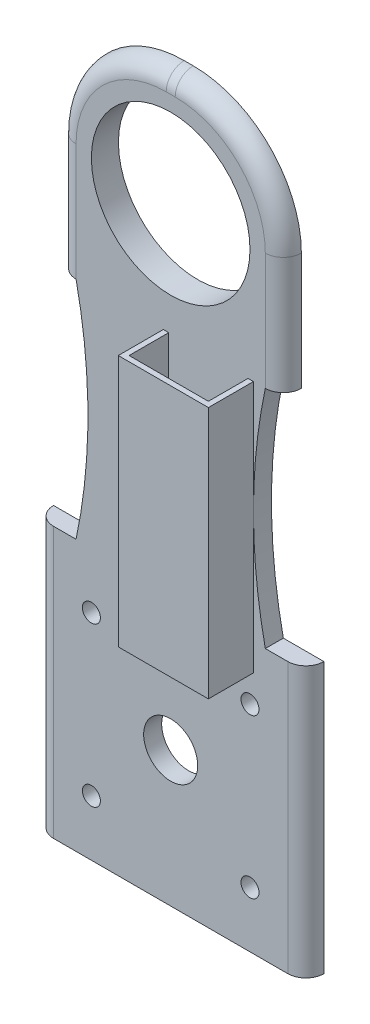
SolidWorks part; units mm, degrees
ref_plane "Front Plane" through (0, 0, 0) normal (0, 0, 1) x (1, 0, 0)
ref_plane "Top Plane" through (0, 0, 0) normal (0, 1, 0) x (1, 0, 0)
ref_plane "Right Plane" through (0, 0, 0) normal (1, 0, 0) x (0, 0, -1)
sketch "Sketch1" plane through (0, 0, 0) normal (0, 0, 1) x (1, 0, 0)
  line L0 (-13.335, -47.625) -> (-19.05, -47.625)
  line L1 (15.875, -15.875) -> (13.335, -15.875)
  line L2 (15.875, -15.875) -> (15.875, 0.635)
  line L3 (0.635, 15.875) -> (-0.635, 15.875)
  line L4 (-15.875, -15.875) -> (-15.875, 0.635)
  line L5 (15.875, -15.875) -> (-15.875, 15.875) construction
  line L6 (15.875, 15.875) -> (-15.875, -15.875) construction
  line L7 (19.05, -85.725) -> (-19.05, -85.725)
  line L8 (19.05, -85.725) -> (19.05, -47.625)
  line L9 (19.05, -47.625) -> (13.335, -47.625)
  line L10 (-19.05, -85.725) -> (-19.05, -47.625)
  line L11 (19.05, -85.725) -> (-19.05, -47.625) construction
  line L12 (19.05, -47.625) -> (-19.05, -85.725) construction
  line L13 (-13.335, -15.875) -> (-15.875, -15.875)
  line L15 (11.176, -77.851) -> (-11.176, -77.851) construction
  line L16 (11.176, -77.851) -> (11.176, -55.499) construction
  line L17 (11.176, -55.499) -> (-11.176, -55.499) construction
  line L18 (-11.176, -77.851) -> (-11.176, -55.499) construction
  line L19 (11.176, -77.851) -> (-11.176, -55.499) construction
  line L20 (11.176, -55.499) -> (-11.176, -77.851) construction
  arc A0 (0.635, 15.875) -> (15.875, 0.635) centre (0.635, 0.635) cw
  arc A1 (-15.875, 0.635) -> (-0.635, 15.875) centre (-0.635, 0.635) cw
  circle A2 centre (0, 0) radius 11.176
  arc A3 (13.335, -15.875) -> (13.335, -47.625) centre (87.863, -31.75) ccw
  arc A4 (-13.335, -15.875) -> (-13.335, -47.625) centre (-87.863, -31.75) cw
  circle A5 centre (11.176, -55.499) radius 1.27
  circle A6 centre (11.176, -77.851) radius 1.27
  circle A7 centre (-11.176, -77.851) radius 1.27
  circle A8 centre (-11.176, -55.499) radius 1.27
  circle A9 centre (0, -66.675) radius 3.81
  point P0 (0, 0)
  point P20 (0, -66.675)
  point P23 (0, -66.675)
  dimension "D3" = 15.24
  dimension "D4" = 22.352
  dimension "D6" = 76.2
  dimension "D11" = 2.54
  dimension "D12" = 7.62
  dimension "D1" = 31.75
  dimension "D2" = 31.75
  dimension "D5" = 31.75
  dimension "D7" = 2.54
  dimension "D8" = 2.54
  dimension "D9" = 38.1
  dimension "D10" = 22.352
extrude "Boss-Extrude1" add sketch "Sketch1" along normal blind 2.54
fillet "Fillet2" radius 2.54 2 edges at (19.05, -66.675, 2.54) (-19.05, -66.675, 2.54)
fillet "Fillet3" radius 2.54 5 edges at (15.875, -7.62, 2.54) (11.4113, 11.4113, 2.54) (0, 15.875, 2.54) (-11.4113, 11.4113, 2.54) (-15.875, -7.62, 2.54)
sketch "Sketch2" plane through (0, 0, 0) normal (0, 0, -1) x (-1, 0, 0)
  circle A0 centre (0, 0) radius 11.176
  circle A1 centre (0, 0) radius 13.716
  circle A2 centre (0, 0) radius 11.176 construction
  dimension "D1" = 2.54
extrude "Boss-Extrude2" add sketch "Sketch2" along normal blind 1.27
sketch "Sketch3" plane through (0, 0, 2.54) normal (0, 0, 1) x (1, 0, 0)
  line L0 (13.335, -15.875) -> (15.875, -15.875) construction
  line L1 (3.535, -22.225) -> (10.901, -22.225)
  line L2 (3.535, -22.225) -> (3.535, -29.591)
  line L3 (3.535, -29.591) -> (10.901, -29.591)
  line L4 (10.901, -22.225) -> (10.901, -29.591)
  line L5 (11.663, -35.5712) -> (11.663, -26.6306) construction
  arc A2 (13.335, -15.875) -> (13.335, -47.625) centre (87.863, -31.75) ccw construction
  dimension "D3" = 0.762
  dimension "D1" = 7.366
  dimension "D2" = 6.35
extrude "Cut-Extrude1" cut sketch "Sketch3" against normal blind 2.54
sketch "Sketch4" plane through (0, 0, 2.54) normal (0, 0, 1) x (1, 0, 0)
  line L0 (16.51, -47.625) -> (13.335, -47.625) construction
  line L1 (-1.037, -15.875) -> (11.663, -15.875)
  line L2 (-1.037, -15.875) -> (-1.037, -51.435)
  line L3 (-1.037, -51.435) -> (11.663, -51.435)
  line L4 (11.663, -15.875) -> (11.663, -51.435)
  arc A0 (13.335, -15.875) -> (13.335, -47.625) centre (87.863, -31.75) ccw construction
  dimension "D1" = 12.7
  dimension "D2" = 3.81
extrude "Extrude-Thin1" add sketch "Sketch4" along normal blind 6.35 thin thin type one direction reverse wall 0.762
sketch "Sketch5" plane through (0, -51.435, 0) normal (0, -1, 0) x (1, 0, 0)
  line L0 (-1.037, 8.89) -> (11.663, 8.89) construction
  line L1 (-0.275, 8.89) -> (10.901, 8.89)
  line L2 (-0.275, 8.89) -> (-0.275, 2.54)
  line L3 (-0.275, 2.54) -> (10.901, 2.54)
  line L4 (10.901, 8.89) -> (10.901, 2.54)
  line L5 (-1.037, 2.54) -> (11.663, 2.54) construction
  line L6 (-1.037, 8.89) -> (-1.037, 2.54) construction
  line L7 (11.663, 8.89) -> (11.663, 2.54) construction
  dimension "D1" = 0.762
  dimension "D2" = 0.762
extrude "Cut-Extrude2" cut sketch "Sketch5" against normal blind 38.1
sketch "Sketch6" plane through (0, 0, 8.89) normal (0, 0, 1) x (1, 0, 0)
  line L1 (-1.037, -15.875) -> (11.663, -15.875)
  line L2 (-1.037, -15.875) -> (-1.037, -51.435)
  line L3 (-1.037, -51.435) -> (11.663, -51.435)
  line L4 (11.663, -15.875) -> (11.663, -51.435)
extrude "Boss-Extrude3" add sketch "Sketch6" against normal blind 0.762
